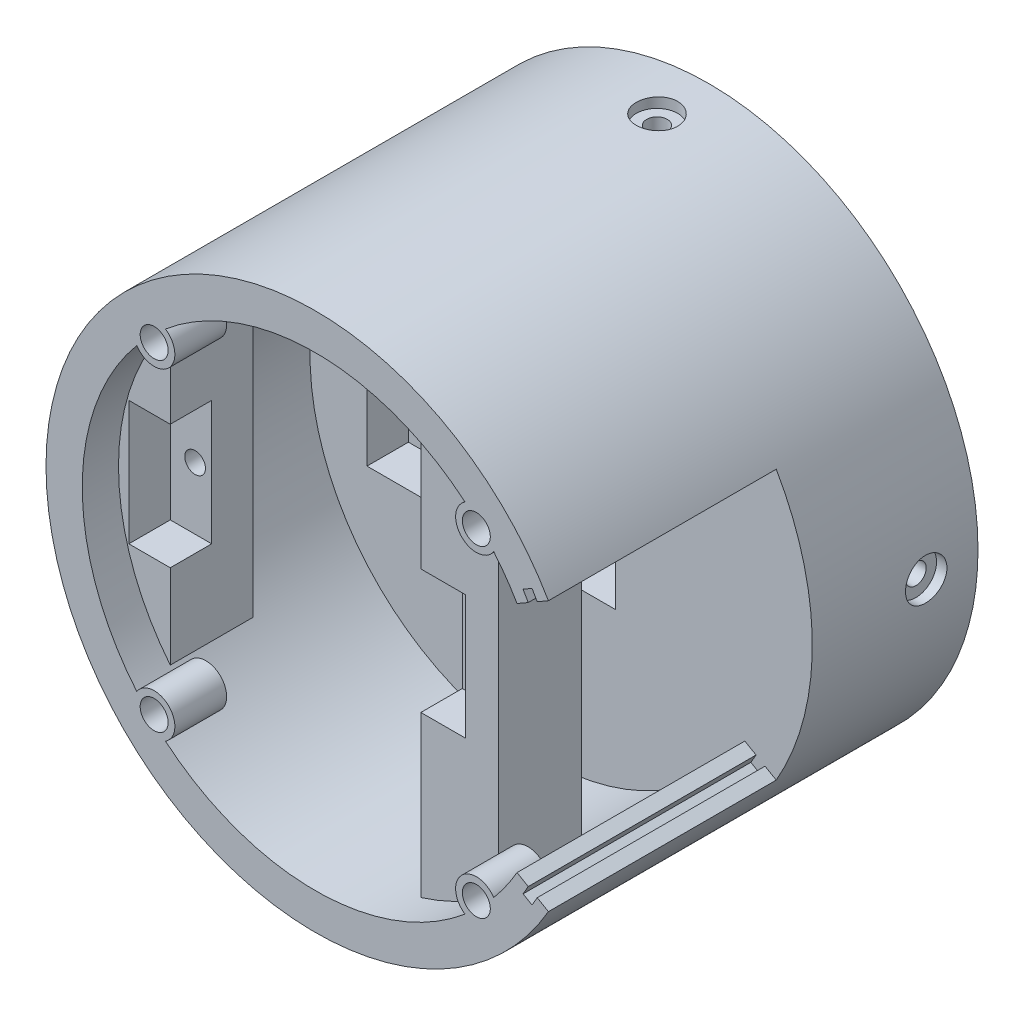
SolidWorks part; units mm, degrees
ref_plane "Спереди" through (0, 0, 0) normal (0, 0, 1) x (1, 0, 0)
ref_plane "Сверху" through (0, 0, 0) normal (0, 1, 0) x (1, 0, 0)
ref_plane "Справа" through (0, 0, 0) normal (1, 0, 0) x (0, 0, -1)
sketch "Эскиз1" plane through (0, 0, 0) normal (0, 0, 1) x (1, 0, 0)
  circle A1 centre (0, 0) radius 26
  dimension "D1" = 52
extrude "Бобышка-Вытянуть1" add sketch "Эскиз1" along normal blind 47
sketch "Эскиз3" plane through (0, 0, 0) normal (0, 0, -1) x (-1, 0, 0)
  circle A0 centre (0, 0) radius 22.5
  dimension "D1" = 45
extrude "Вырез-Вытянуть1" cut sketch "Эскиз3" against normal blind 20 contours A0
sketch "Эскиз10" plane through (0, 0, 20) normal (0, 0, -1) x (-1, 0, 0)
  circle A0 centre (0, 0) radius 15
  dimension "D1" = 30
sketch "Эскиз4" plane through (0, 0, 47) normal (0, 0, 1) x (1, 0, 0)
  circle A0 centre (0, 0) radius 22.5
  dimension "D1" = 45
extrude "Вырез-Вытянуть2" cut sketch "Эскиз4" against normal offset from surface (22 mm away) 5 up to face at (-22.5, 0, 20)
sketch "Эскиз13" plane through (0, 0, 25) normal (0, 0, 1) x (1, 0, 0)
  line L0 (0, 26) -> (0, -26) construction
  line L1 (-26, 0) -> (26, 0) construction
  line L3 (-17, 6.5) -> (7, 6.5)
  line L4 (-17, 6.5) -> (-17, -6.5)
  line L5 (-17, -6.5) -> (7, -6.5)
  line L6 (7, 6.5) -> (7, -6.5)
  circle A0 centre (0, 0) radius 26 construction
  point P11 (-17, 0)
  point P13 (-5, 6.5)
  dimension "D1" = 13
  dimension "D2" = 24
  dimension "D3" = 5
extrude "Вырез-Вытянуть3" cut sketch "Эскиз13" against normal blind 4
sketch "Эскиз12" plane through (0, 0, 47) normal (0, 0, 1) x (1, 0, 0)
  line L0 (0, 26) -> (0, -26) construction
  line L1 (0, 0) -> (28.1458, 16.25) construction
  line L2 (-26, 0) -> (32.5, 0) construction
  line L5 (19.4856, 11.25) -> (22.5167, 13)
  line L6 (19.4856, -11.25) -> (22.5167, -13)
  circle A0 centre (0, 0) radius 26 construction
  arc A4 (19.4856, -11.25) -> (19.4856, 11.25) centre (0, 0) ccw
  arc A6 (22.5167, -13) -> (22.5167, 13) centre (0, 0) ccw
  circle M4 centre (0, 0) radius 26
  circle M9 centre (0, 0) radius 22.5
  dimension "D1" = 30
extrude "Вырез-Вытянуть4" cut sketch "Эскиз12" along direction (0, 0, -1) on the side against the normal up to surface (22 mm away) contours M4 M9 region at (23.1972, 0, 47) up to face at (-22.5, 0, 25)
ref_plane "Плоскость2" through (0, 0, 35.5) normal (0, 0, 1) x (1, 0, 0)
sketch "Эскиз14" plane through (0, 0, 35.5) normal (0, 0, 1) x (1, 0, 0)
  line L1 (7, 0) -> (-46.5151, 0) construction
  line L2 (7, -6.5) -> (7, 6.5) construction
  line L3 (-17.5, -28.5313) -> (-17.5, 17.8536) construction
  line L6 (7, 0) -> (57.6607, 0) construction
  line L8 (14.2, -44.5711) -> (14.2, 20) construction
  line L10 (14.2, -20.5757) -> (14.2, 20.5757)
  line L13 (-17.5, -17.8536) -> (-17.5, 17.8536)
  line L15 (6.7, -24.0855) -> (6.7, 24.0855)
  line L16 (0, -28.5313) -> (0, 28.5313) construction
  arc A4 (-17.5, 17.8536) -> (-17.5, -17.8536) centre (0, 0) ccw
  arc A5 (14.2, 20.5757) -> (6.7, 24.0855) centre (0, 0) ccw
  arc A6 (6.7, -24.0855) -> (14.2, -20.5757) centre (0, 0) ccw
  point P11 (-17.5, 0)
  point P18 (7, 0)
  point P22 (14.2, 0)
  point P27 (14.2, 0)
  point P29 (-17.5, 0)
  point P33 (7.5, 0)
  point P34 (6.7, 0)
  point P35 (0, 0)
  dimension "D1" = 17.5
  dimension "D4" = 6.7
extrude "Бобышка-Вытянуть2" add sketch "Эскиз14" along normal blind 8
sketch "Эскиз15" plane through (0, 0, 43.5) normal (0, 0, 1) x (1, 0, 0)
  line L0 (43.3889, 0) -> (-43.3889, 0) construction
  line L1 (0, 36.1435) -> (0, -36.1435) construction
  line L2 (-21.5, 29.8665) -> (-21.5, -29.8665) construction
  line L3 (11, 32.0712) -> (11, -32.0712) construction
  line L4 (-17.5, 23.7559) -> (-17.5, -23.2484) construction
  line L5 (-21.5, -6) -> (-21.5, 6)
  line L6 (-21.5, 6) -> (-17.5, 6)
  line L7 (6.7, 41.39) -> (6.7, -19.4927) construction
  line L8 (6.7, 21.4793) -> (6.7, -21.4793) construction
  line L9 (11, -6) -> (11, 6)
  line L10 (11, 6) -> (6.7, 6)
  line L11 (-17.5, 6) -> (-17.5, -6)
  line L12 (6.7, 6) -> (6.7, -6)
  line L13 (11, -6) -> (6.7, -6)
  line L14 (-21.5, -6) -> (-17.5, -6)
  point P4 (0, 0)
  point P8 (0, 0)
  point P11 (-21.5, 0)
  point P14 (11, 0)
  point P19 (-17.5, 0.2537)
  point P24 (6.7, 10.9487)
  point P30 (6.7, 0)
  point P31 (11, 0)
  point P32 (-17.5, 0)
  point P33 (-21.5, 0)
  dimension "D1" = 21.5
  dimension "D2" = 11
  dimension "D3" = 6
  dimension "D4" = 6
extrude "Вырез-Вытянуть5" cut sketch "Эскиз15" along direction (0, 0, 1) on the side against the normal offset from surface (4 mm away) 18.5 up to face at (-5, 0, 21)
sketch "Эскиз17" plane through (0, 0, 39.5) normal (0, 0, 1) x (1, 0, 0)
  circle A1 centre (-19.1, 0) radius 1
  circle A2 centre (8.6, 0) radius 1
extrude "Вырез-Вытянуть6" cut sketch "Эскиз17" along direction (0, 0, 1) on the side against the normal up to surface (4 mm away) up to face at (10.5461, 0, 35.5)
sketch "Эскиз20" plane through (0, 0, 47) normal (0, 0, 1) x (1, 0, 0)
  line L0 (-57.2124, 0) -> (57.2124, 0) construction
  line L1 (0, 34.3681) -> (0, -34.3681) construction
  line L2 (0, 0) -> (-44.2288, 44.2288) construction
  circle A0 centre (0, 0) radius 22 construction
  circle A2 centre (0, 0) radius 26 construction
  circle A3 centre (-15.5563, 15.5563) radius 2
  circle A4 centre (15.5563, 15.5563) radius 2
  circle A5 centre (15.5563, -15.5563) radius 2
  circle A6 centre (-15.5563, -15.5563) radius 2
  point P3 (-15.5563, 15.5563)
  point P8 (0, 0)
  point P12 (0, 0)
  point P23 (0, 0)
  point P27 (0, 0)
  dimension "D2" = 52
  dimension "D3" = 22
  dimension "D1" = 4
  dimension "D4" = 4
extrude "Бобышка-Вытянуть3" add sketch "Эскиз20" against normal blind 5
sketch "Эскиз21" plane through (0, 0, 47) normal (0, 0, 1) x (1, 0, 0)
  circle A4 centre (-15.5563, 15.5563) radius 1.35
  circle A5 centre (15.5563, 15.5563) radius 1.35
  circle A6 centre (15.5563, -15.5563) radius 1.35
  circle A7 centre (-15.5563, -15.5563) radius 1.35
  point P12 (0, 0)
  point P14 (0, 0)
  dimension "D1" = 2.7
  dimension "D2" = 4
extrude "Вырез-Вытянуть9" cut sketch "Эскиз21" against normal blind 5
sketch "Эскиз22" plane through (0, 0, 0) normal (0.5, -0.866, 0) x (0.866, 0.5, 0)
  line L0 (24.25, 47) -> (24.25, 25) construction
  line L1 (22.5, 47) -> (26, 47) construction
  line L2 (22.5, 25) -> (26, 25) construction
  line L3 (24.75, 47) -> (23.75, 47)
  line L4 (23.75, 47) -> (23.75, 25)
  line L5 (26, 25) -> (13, 25) construction
  line L6 (23.75, 25) -> (24.75, 25)
  line L7 (24.75, 47) -> (24.75, 25)
  dimension "D1" = 0.5
extrude "Вырез-Вытянуть10" cut sketch "Эскиз22" against normal blind 1
sketch "Эскиз23" plane through (0, 0, 0) normal (0.5, 0.866, 0) x (0.866, -0.5, 0)
  line L0 (24.25, -25) -> (24.25, -47) construction
  line L1 (22.5, -25) -> (26, -25) construction
  line L2 (22.5, -47) -> (26, -47) construction
  line L3 (24.75, -25) -> (23.75, -25)
  line L4 (23.75, -25) -> (23.75, -47)
  line L5 (23.75, -47) -> (24.75, -47)
  line L6 (24.75, -25) -> (24.75, -47)
  dimension "D1" = 0.5
extrude "Вырез-Вытянуть11" cut sketch "Эскиз23" against normal blind 1
extrude "Вырез-Вытянуть12" cut sketch "Эскиз1<4>" along normal blind 9
sketch "Эскиз1<4>" plane through (0, 0, 0) normal (0, 0, 1) x (1, 0, 0) same geometry as "Эскиз1"
chamfer "Фаска1" distance 1 angle 45 1 edges at (22.5, 0, 9)
hole_wizard "Отверстие1" positions "Трехмерный эскиз1" profile "Эскиз25" legacy
sketch3d "Трехмерный эскиз1"
  line L0 (26, 0, 9) -> (0, 0, 9) construction
  line L1 (0, 0, 25) -> (0, 0, 9) construction
  line L3 (0, 0, 9) -> (0, -26, 9) construction
  line L5 (0, -26, 9) -> (0, -26, 14) construction
  circle A0 centre (0, 0, 9) radius 26 construction
  point P0 (0, -26, 14)
  point P7 (0, 0, 35)
  dimension "D1" = 90
  dimension "D2" = 5
sketch "Эскиз25" plane through (0, -26, 14) normal (1, 0, 0) x (0, 0, -1)
  line L0 (0, 0) -> (0, 5)
  line L1 (0, 5) -> (1, 5)
  line L2 (1, 5) -> (1, 1)
  line L3 (1, 1) -> (2, 1)
  line L4 (2, 1) -> (2, 0)
  line L5 (2, 0) -> (0, 0)
  line L6 (0, 110) -> (0, -10) construction
  dimension "Диаметр" = 2
  dimension "Глубина" = 5
  dimension "Диа. цековки" = 4
  dimension "Глуб. цековки" = 1
pattern_circular "Круговой массив1" count 4 over 360 about axis through (0, 0, 47) along (0, 0, -1) of "Отверстие1" reverse direction yes
